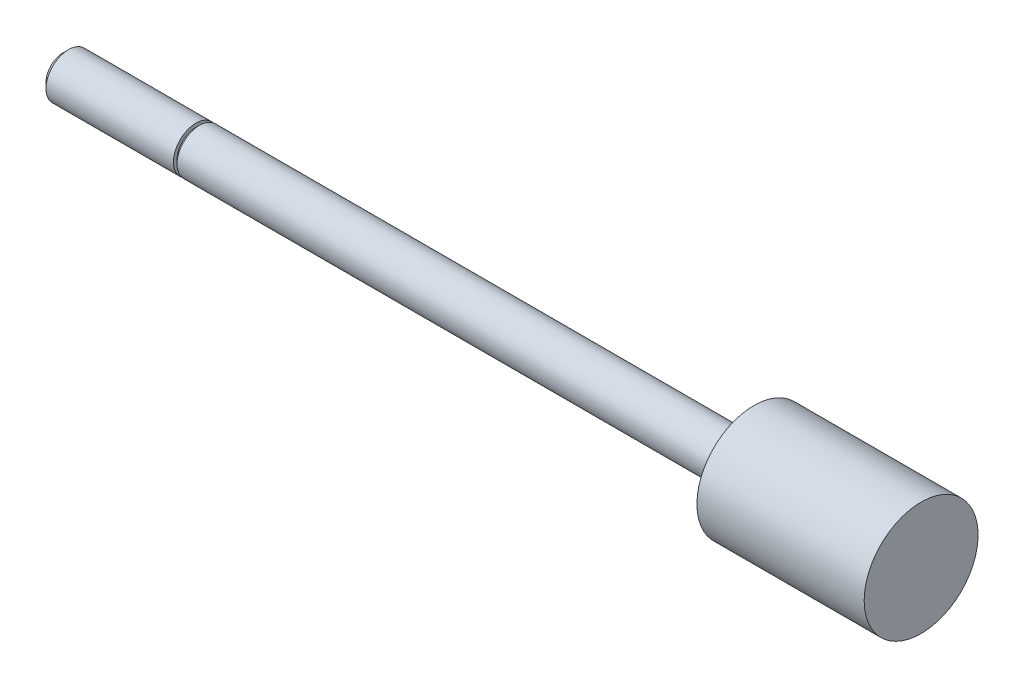
SolidWorks part; units mm, degrees
ref_plane "Front Plane" through (0, 0, 0) normal (0, 0, 1) x (1, 0, 0)
ref_plane "Top Plane" through (0, 0, 0) normal (0, 1, 0) x (1, 0, 0)
ref_plane "Right Plane" through (0, 0, 0) normal (1, 0, 0) x (0, 0, -1)
sketch "Sketch1" plane through (0, 0, 0) normal (0, 0, 1) x (1, 0, 0)
  line L0 (0, 0) -> (0, 1.5875)
  line L1 (0, 1.5875) -> (39.243, 1.5875)
  line L2 (39.243, 1.5875) -> (39.243, 4.0323)
  line L3 (39.243, 4.0323) -> (51.0794, 4.0323)
  line L4 (51.0794, 4.0323) -> (51.0794, 0)
  line L5 (51.0794, 0) -> (0, 0)
  line L6 (51.0794, 0) -> (0, 0) construction
revolve "Revolve1" add sketch "Sketch1" angle 360 about L6 reverse direction yes
cosmetic thread "Cosmetic Thread1" parameters "D1"=9.652, "D2"=2.4181
sketch "Sketch2" plane through (0, 0, 0) normal (0, 0, 1) x (1, 0, 0)
  line L0 (-9.652, 0) -> (-9.652, 1.209)
  line L1 (-9.652, 1.209) -> (-9.2735, 1.5875)
  line L2 (-9.2735, 1.5875) -> (0, 1.5875)
  line L3 (0, 1.5875) -> (0, 0)
  line L4 (0, 0) -> (-9.652, 0)
  line L5 (0, 0) -> (-9.652, 0) construction
revolve "Revolve2" add sketch "Sketch2" angle 360 about L5 reverse direction yes
ref_plane "Plane1" through (0, 0, 0) normal (1, 0, 0) x (0, 0, -1)
ref_plane "Plane2" through (0, 0, 0) normal (1, 0, 0) x (0, 0, -1)
ref_plane "Plane3" through (90.3224, 0, 0) normal (1, 0, 0) x (0, 0, -1)
ref_plane "Plane4" through (-9.652, 0, 0) normal (1, 0, 0) x (0, 0, -1)
sketch "Sketch3" plane through (0, 0, 0) normal (0, 0, 1) x (1, 0, 0)
  line L0 (-0.254, 1.3335) -> (0, 1.3335)
  line L1 (0, 1.3335) -> (0, 1.8415)
  line L2 (0, 1.8415) -> (-0.254, 1.8415)
  line L3 (-0.254, 1.8415) -> (-0.254, 1.3335)
  line L4 (0, 0) -> (-0.254, 0) construction
revolve "Cut-Revolve1" cut sketch "Sketch3" angle 360 about L4 reverse direction yes
ref_plane "Plane5" through (0, 0, 0) normal (1, 0, 0) x (0, 0, -1)
ref_plane "Plane6" through (0, 0, 0) normal (1, 0, 0) x (0, 0, -1)
ref_plane "Plane7" through (-9.652, 0, 0) normal (1, 0, 0) x (0, 0, -1)
ref_plane "dia1 XY" through (0, 0, 0) normal (1, 0, 0) x (0, 0, -1)
ref_plane "dia1 XZ" through (0, 1.5875, 0) normal (0, -1, 0) x (-1, 0, 0)
ref_plane "dia1 YZ" through (0, 0, 0) normal (0, 0, -1) x (-1, 0, 0)
ref_axis "dia1 X" through (0, 1.5875, 80.9) along (0, 0, -1)
ref_axis "dia1 Y" through (0, -50, 0) along (0, 1, 0)
ref_axis "dia1 Z" through (80.9, 1.5875, 0) along (-1, 0, 0)
sketch3d "dia1"
  point P0 (0, 1.5875, 0)
ref_plane "dia12 XY" through (0, 0, 0) normal (1, 0, 0) x (0, 0, -1)
ref_plane "dia12 XZ" through (0, 0, 0) normal (0, -1, 0) x (-1, 0, 0)
ref_plane "dia12 YZ" through (0, 0, 7.6835) normal (0, 0, -1) x (-1, 0, 0)
ref_axis "dia12 X" through (0, 0, 80.9) along (0, 0, -1)
ref_axis "dia12 Y" through (0, -50, 7.6835) along (0, 1, 0)
ref_axis "dia12 Z" through (80.9, 0, 7.6835) along (-1, 0, 0)
sketch3d "dia12"
  point P0 (0, 0, 7.6835)
ref_plane "dia1r XY" through (0, 0, 0) normal (1, 0, 0) x (0, 0, -1)
ref_plane "dia1r XZ" through (0, 0, 0) normal (0, -1, 0) x (-1, 0, 0)
ref_plane "dia1r YZ" through (0, 0, 5.5626) normal (0, 0, -1) x (-1, 0, 0)
ref_axis "dia1r X" through (0, 0, 80.9) along (0, 0, -1)
ref_axis "dia1r Y" through (0, -50, 5.5626) along (0, 1, 0)
ref_axis "dia1r Z" through (80.9, 0, 5.5626) along (-1, 0, 0)
sketch3d "dia1r"
  point P0 (0, 0, 5.5626)
ref_plane "dia2 XY" through (0, 0, 0) normal (1, 0, 0) x (0, 0, -1)
ref_plane "dia2 XZ" through (0, -1.5875, 0) normal (0, -1, 0) x (-1, 0, 0)
ref_plane "dia2 YZ" through (0, 0, 0) normal (0, 0, -1) x (-1, 0, 0)
ref_axis "dia2 X" through (0, -1.5875, 80.9) along (0, 0, -1)
ref_axis "dia2 Y" through (0, -50, 0) along (0, 1, 0)
ref_axis "dia2 Z" through (80.9, -1.5875, 0) along (-1, 0, 0)
sketch3d "dia2"
  point P0 (0, -1.5875, 0)
ref_plane "dia22 XY" through (0, 0, 0) normal (1, 0, 0) x (0, 0, -1)
ref_plane "dia22 XZ" through (0, 0, 0) normal (0, -1, 0) x (-1, 0, 0)
ref_plane "dia22 YZ" through (0, 0, -7.6835) normal (0, 0, -1) x (-1, 0, 0)
ref_axis "dia22 X" through (0, 0, 80.9) along (0, 0, -1)
ref_axis "dia22 Y" through (0, -50, -7.6835) along (0, 1, 0)
ref_axis "dia22 Z" through (80.9, 0, -7.6835) along (-1, 0, 0)
sketch3d "dia22"
  point P0 (0, 0, -7.6835)
ref_plane "dia2r XY" through (0, 0, 0) normal (1, 0, 0) x (0, 0, -1)
ref_plane "dia2r XZ" through (0, 0, 0) normal (0, -1, 0) x (-1, 0, 0)
ref_plane "dia2r YZ" through (0, 0, -5.5626) normal (0, 0, -1) x (-1, 0, 0)
ref_axis "dia2r X" through (0, 0, 80.9) along (0, 0, -1)
ref_axis "dia2r Y" through (0, -50, -5.5626) along (0, 1, 0)
ref_axis "dia2r Z" through (80.9, 0, -5.5626) along (-1, 0, 0)
sketch3d "dia2r"
  point P0 (0, 0, -5.5626)
ref_plane "rl1 XY" through (-9.652, 0, 0) normal (1, 0, 0) x (0, 0, -1)
ref_plane "rl1 XZ" through (0, 0, 0) normal (0, -1, 0) x (-1, 0, 0)
ref_plane "rl1 YZ" through (0, 0, 0) normal (0, 0, -1) x (-1, 0, 0)
ref_axis "rl1 X" through (-9.652, 0, 80.9) along (0, 0, -1)
ref_axis "rl1 Y" through (-9.652, -50, 0) along (0, 1, 0)
ref_axis "rl1 Z" through (80.9, 0, 0) along (-1, 0, 0)
sketch3d "rl1"
  point P0 (-9.652, 0, 0)
ref_plane "rl2 XY" through (0, 0, 0) normal (1, 0, 0) x (0, 0, -1)
ref_plane "rl2 XZ" through (0, 0, 0) normal (0, -1, 0) x (-1, 0, 0)
ref_plane "rl2 YZ" through (0, 0, 0) normal (0, 0, -1) x (-1, 0, 0)
ref_axis "rl2 X" through (0, 0, 80.9) along (0, 0, -1)
ref_axis "rl2 Y" through (0, -50, 0) along (0, 1, 0)
ref_axis "rl2 Z" through (80.9, 0, 0) along (-1, 0, 0)
sketch3d "rl2"
  point P0 (0, 0, 0)
ref_plane "rod_cp XY" through (0, 0, 0) normal (1, 0, 0) x (0, 0, -1)
ref_plane "rod_cp XZ" through (0, 0, 0) normal (0, -1, 0) x (-1, 0, 0)
ref_plane "rod_cp YZ" through (0, 0, 0) normal (0, 0, -1) x (-1, 0, 0)
ref_axis "rod_cp X" through (0, 0, 80.9) along (0, 0, -1)
ref_axis "rod_cp Y" through (0, -50, 0) along (0, 1, 0)
ref_axis "rod_cp Z" through (80.9, 0, 0) along (-1, 0, 0)
sketch3d "rod_cp"
  point P0 (0, 0, 0)
ref_plane "thd1 XY" through (-9.652, 0, 0) normal (1, 0, 0) x (0, 0, -1)
ref_plane "thd1 XZ" through (0, 1.5875, 0) normal (0, -1, 0) x (-1, 0, 0)
ref_plane "thd1 YZ" through (0, 0, 0) normal (0, 0, -1) x (-1, 0, 0)
ref_axis "thd1 X" through (-9.652, 1.5875, 80.9) along (0, 0, -1)
ref_axis "thd1 Y" through (-9.652, -50, 0) along (0, 1, 0)
ref_axis "thd1 Z" through (80.9, 1.5875, 0) along (-1, 0, 0)
sketch3d "thd1"
  point P0 (-9.652, 1.5875, 0)
ref_plane "thd2 XY" through (-9.652, 0, 0) normal (1, 0, 0) x (0, 0, -1)
ref_plane "thd2 XZ" through (0, -1.5875, 0) normal (0, -1, 0) x (-1, 0, 0)
ref_plane "thd2 YZ" through (0, 0, 0) normal (0, 0, -1) x (-1, 0, 0)
ref_axis "thd2 X" through (-9.652, -1.5875, 80.9) along (0, 0, -1)
ref_axis "thd2 Y" through (-9.652, -50, 0) along (0, 1, 0)
ref_axis "thd2 Z" through (80.9, -1.5875, 0) along (-1, 0, 0)
sketch3d "thd2"
  point P0 (-9.652, -1.5875, 0)
ref_plane "to_rod_clevis XY" through (-9.652, 0, 0) normal (1, 0, 0) x (0, 0, -1)
ref_plane "to_rod_clevis XZ" through (0, 0, 0) normal (0, -1, 0) x (-1, 0, 0)
ref_plane "to_rod_clevis YZ" through (0, 0, 0) normal (0, 0, -1) x (-1, 0, 0)
ref_axis "to_rod_clevis X" through (-9.652, 0, 80.9) along (0, 0, -1)
ref_axis "to_rod_clevis Y" through (-9.652, -50, 0) along (0, 1, 0)
ref_axis "to_rod_clevis Z" through (80.9, 0, 0) along (-1, 0, 0)
sketch3d "to_rod_clevis"
  point P0 (-9.652, 0, 0)
